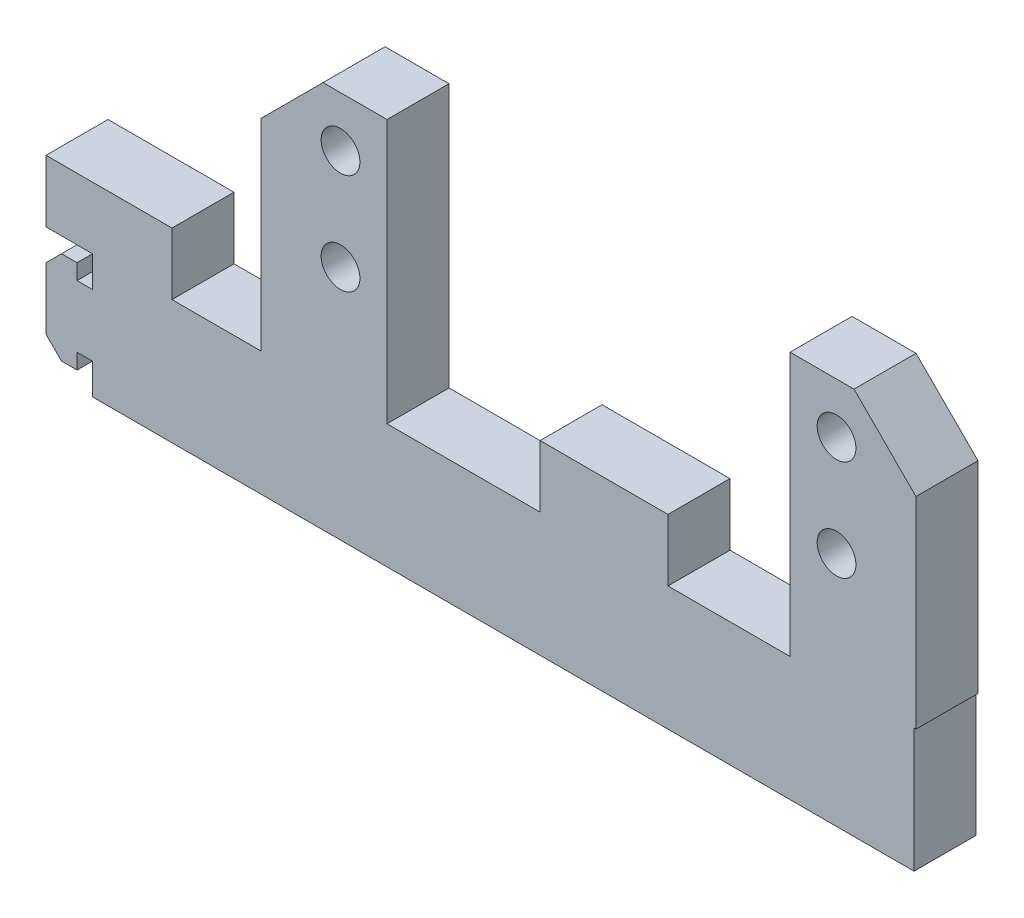
SolidWorks part; units mm, degrees
ref_plane "Front Plane" through (0, 0, 0) normal (0, 0, 1) x (1, 0, 0)
ref_plane "Top Plane" through (0, 0, 0) normal (0, 1, 0) x (1, 0, 0)
ref_plane "Right Plane" through (0, 0, 0) normal (1, 0, 0) x (0, 0, -1)
sketch "Sketch1" plane through (0, 136.6763, 0) normal (0, 1, 0) x (1, 0, 0)
  line L0 (-27.651, -32.4827) -> (-27.651, -60.4545) construction
  line L1 (-103.851, -54.1033) -> (-90.951, -54.1033)
  line L2 (-103.851, -54.1033) -> (-103.851, -60.4533)
  line L3 (-103.851, -60.4533) -> (-90.951, -60.4533)
  line L4 (-90.951, -54.1033) -> (-90.951, -60.4533)
  line L5 (-68.926, -54.1033) -> (-81.826, -54.1033)
  line L6 (-68.926, -54.1033) -> (-68.926, -60.4533)
  line L7 (-68.926, -60.4533) -> (-81.826, -60.4533)
  line L8 (-81.826, -54.1033) -> (-81.826, -60.4533)
  line L9 (-53.251, -54.1033) -> (-40.151, -54.1033)
  line L10 (-53.251, -54.1033) -> (-53.251, -60.4533)
  line L11 (-53.251, -60.4533) -> (-40.151, -60.4533)
  line L12 (-40.151, -54.1033) -> (-40.151, -60.4533)
  line L13 (-27.651, -54.1033) -> (-14.751, -54.1033)
  line L14 (-27.651, -54.1033) -> (-27.651, -60.4533)
  line L15 (-27.651, -60.4533) -> (-14.751, -60.4533)
  line L16 (-14.751, -54.1033) -> (-14.751, -60.4533)
  dimension "D1" = 12.9
  dimension "D2" = 13.1
  dimension "D3" = 12.9
  dimension "D4" = 12.9
  dimension "D5" = 50.6
extrude "Boss-Extrude1" add sketch "Sketch1" against normal blind 6.35
sketch "Sketch2" plane through (0, 130.3263, 0) normal (0, -1, 0) x (-1, 0, 0)
  line L1 (103.851, -60.4533) -> (14.951, -60.4533)
  line L2 (103.851, -60.4533) -> (103.851, -54.1033)
  line L3 (103.851, -54.1033) -> (14.951, -54.1033)
  line L4 (14.951, -60.4533) -> (14.951, -54.1033)
  dimension "D1" = 6.35
  dimension "D2" = 88.9
extrude "Boss-Extrude2" add sketch "Sketch2" along normal blind 12.7
sketch "Sketch3" plane through (0, 136.6763, 0) normal (0, 1, 0) x (1, 0, 0)
  line L1 (-68.926, -54.1033) -> (-81.826, -54.1033)
  line L2 (-68.926, -54.1033) -> (-68.926, -60.4533)
  line L3 (-68.926, -60.4533) -> (-81.826, -60.4533)
  line L4 (-81.826, -54.1033) -> (-81.826, -60.4533)
  line L5 (-14.751, -54.1033) -> (-27.651, -54.1033)
  line L6 (-14.751, -54.1033) -> (-14.751, -60.4533)
  line L7 (-14.751, -60.4533) -> (-27.651, -60.4533)
  line L8 (-27.651, -54.1033) -> (-27.651, -60.4533)
extrude "Boss-Extrude3" add sketch "Sketch3" along normal up to surface (20.6375 mm away)
chamfer "Chamfer1" distance 6.35 angle 45 2 edges at (-14.751, 157.3138, 57.2783) (-81.826, 157.3138, 57.2783)
sketch "Sketch4" plane through (0, 0, 60.4533) normal (0, 0, 1) x (1, 0, 0)
  circle A0 centre (-73.6885, 152.1544) radius 1.9844
  circle A1 centre (-73.6885, 141.8357) radius 1.9844
  circle A2 centre (-22.8885, 141.8357) radius 1.9844
  circle A3 centre (-22.8885, 152.1544) radius 1.9844
extrude "Cut-Extrude1" cut sketch "Sketch4" against normal through all
sketch "Sketch5" plane through (0, 0, 60.4533) normal (0, 0, 1) x (1, 0, 0)
  line L0 (-14.951, 123.9763) -> (-2.251, 117.6263)
  line L1 (-14.951, 117.6263) -> (-14.951, 130.3263) construction
  line L2 (-14.951, 117.6263) -> (-103.851, 117.6263) construction
  line L3 (-2.251, 117.6263) -> (-14.951, 117.6263)
  line L4 (-14.951, 117.6263) -> (-14.951, 123.9763)
  dimension "D1" = 12.7
sketch "Sketch8" plane through (0, 0, 60.4533) normal (0, 0, 1) x (1, 0, 0)
  line L0 (-103.851, 123.9763) -> (-14.951, 123.9763) construction
  line L1 (-103.851, 117.6263) -> (-103.851, 136.6763) construction
  line L2 (-99.0885, 117.6263) -> (-99.0885, 120.8013)
  line L3 (-103.851, 130.3263) -> (-102.9247, 130.3263)
  line L4 (-103.851, 130.3263) -> (-103.851, 128.7388)
  line L5 (-103.851, 128.7388) -> (-100.676, 128.7388)
  line L6 (-103.851, 117.6263) -> (-102.9247, 117.6263)
  line L7 (-103.851, 130.3263) -> (-100.676, 128.7388) construction
  line L8 (-103.851, 128.7388) -> (-102.9247, 130.3263) construction
  line L9 (-102.9247, 130.3263) -> (-99.0885, 130.3263)
  line L10 (-100.676, 128.7388) -> (-100.676, 127.1513)
  line L11 (-100.676, 127.1513) -> (-99.0885, 127.1513)
  line L12 (-99.0885, 130.3263) -> (-99.0885, 127.1513)
  line L13 (-102.9247, 130.3263) -> (-99.0885, 127.1513) construction
  line L14 (-100.676, 127.1513) -> (-99.0885, 130.3263) construction
  line L15 (-102.9247, 117.6263) -> (-99.0885, 117.6263)
  line L16 (-103.851, 117.6263) -> (-103.851, 119.2138)
  line L17 (-103.851, 119.2138) -> (-100.676, 119.2138)
  line L18 (-100.676, 119.2138) -> (-100.676, 120.8013)
  line L19 (-100.676, 120.8013) -> (-99.0885, 120.8013)
  point P9 (-103.1339, 129.9678)
  point P13 (-100.2113, 128.0806)
  dimension "D1" = 6.35
  dimension "D2" = 4.7625
  dimension "D3" = 3.175
  dimension "D4" = 1.5875
  dimension "D5" = 3.175
  dimension "D6" = 3.175
extrude "Cut-Extrude3" cut sketch "Sketch8" against normal through all
sketch "Sketch9" plane through (0, 0, 60.4533) normal (0, 0, 1) x (1, 0, 0)
  line L0 (-14.951, 117.6263) -> (-99.0885, 117.6263) construction
  circle A0 centre (-103.851, 117.6263) radius 4.7625
  dimension "D1" = 9.525
chamfer "Chamfer2" distance 1.5875 angle 45 2 edges at (-103.851, 128.7388, 57.2783) (-103.851, 119.2138, 57.2783)
